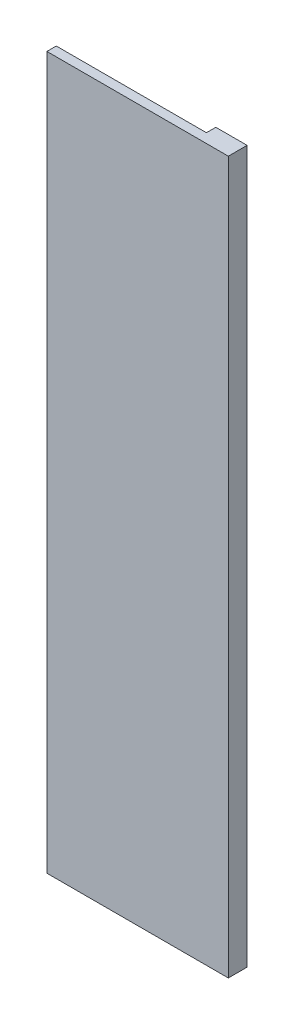
SolidWorks part; units mm, degrees
ref_plane "Front Plane" through (0, 0, 0) normal (0, 0, 1) x (1, 0, 0)
ref_plane "Top Plane" through (0, 0, 0) normal (0, 1, 0) x (1, 0, 0)
ref_plane "Right Plane" through (0, 0, 0) normal (1, 0, 0) x (0, 0, -1)
sketch "Sketch1" plane through (0, 0, 0) normal (0, 0, 1) x (1, 0, 0)
  line L0 (-48, 0) -> (48, 0) construction
  line L1 (-48, 435) -> (68, 435)
  line L2 (-48, 435) -> (-48, -20)
  line L3 (-48, -20) -> (68, -20)
  line L4 (68, 435) -> (68, -20)
  line L5 (48, 435) -> (48, 0) construction
  line L7 (48, 435) -> (-48, 435)
  line L8 (48, 435) -> (48, 0)
  line L9 (48, 0) -> (-48, 0)
  line L10 (-48, 435) -> (-48, 0)
  dimension "D1" = 20
  dimension "D2" = 20
extrude "Boss-Extrude1" add sketch "Sketch1" against normal blind 6 contours L8 L9 L2 L3 L4 L1 region at (58, 430.3045, 0)
sketch "Sketch2" plane through (0, 0, 0) normal (0, 0, 1) x (1, 0, 0)
  line L1 (68, -20) -> (-48, -20)
  line L2 (68, -20) -> (68, 435)
  line L3 (68, 435) -> (-48, 435)
  line L4 (-48, -20) -> (-48, 435)
extrude "Boss-Extrude2" add sketch "Sketch2" along normal blind 6
